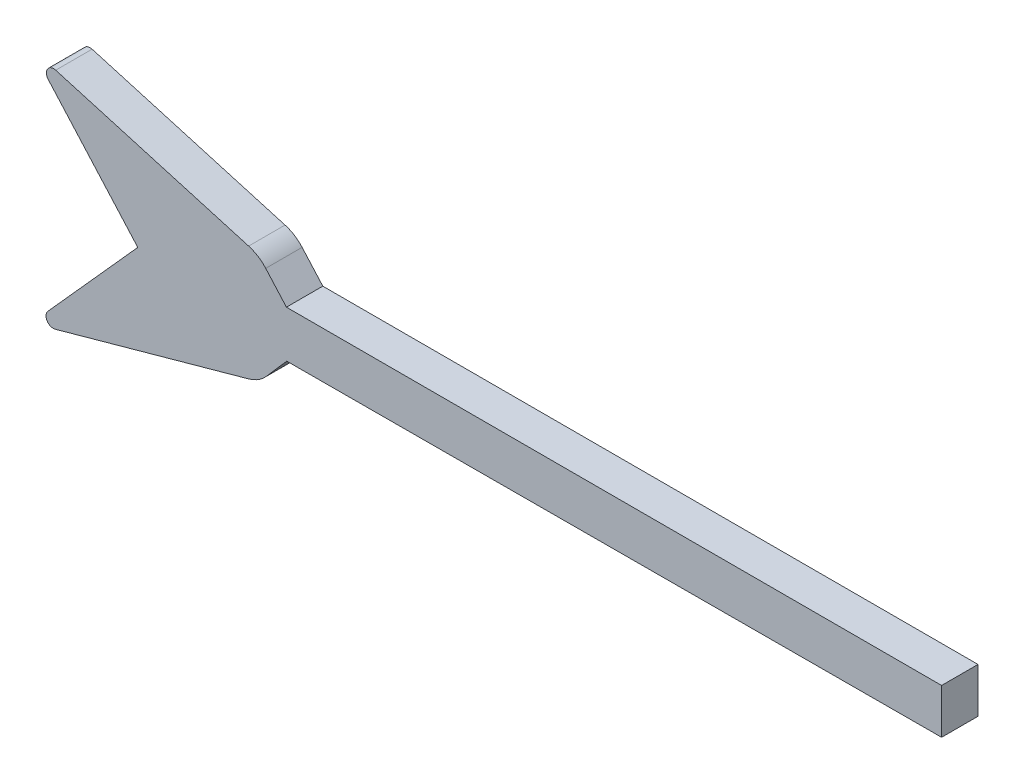
SolidWorks part; units mm, degrees
ref_plane "Plan de face" through (0, 0, 0) normal (0, 0, 1) x (1, 0, 0)
ref_plane "Plan de dessus" through (0, 0, 0) normal (0, 1, 0) x (1, 0, 0)
ref_plane "Plan de droite" through (0, 0, 0) normal (1, 0, 0) x (0, 0, -1)
sketch "Esquisse1" plane through (0, 0, 0) normal (0, 0, 1) x (1, 0, 0)
  line L0 (-12.4551, 7.3291) -> (-23.8324, 20.1144)
  line L1 (-28.5223, 23.0723) -> (-81.5296, 38.4159)
  line L2 (-83.5798, 35.1652) -> (-58.9831, 7.5246)
  line L3 (-58.9831, 7.5246) -> (-83.6838, -20.0231)
  line L4 (-81.6598, -23.2854) -> (-28.5015, -8.5304)
  line L5 (-23.6466, -5.4756) -> (-12.4551, 7.3291)
  line L6 (-18.1437, 13.7217) -> (161.8563, 13.7217)
  line L7 (161.8563, 13.7217) -> (161.8563, 1.3786)
  line L8 (161.8563, 1.3786) -> (-18.0508, 0.9268)
  line L9 (-18.0508, 0.9268) -> (-12.4551, 7.3291)
  arc A0 (-83.6838, -20.0231) -> (-81.6598, -23.2854) centre (-82.1948, -21.3582) ccw
  arc A1 (-81.5296, 38.4159) -> (-83.5798, 35.1652) centre (-82.0857, 36.4947) ccw
  arc A2 (-28.5015, -8.5304) -> (-23.6466, -5.4756) centre (-31.176, 1.1053) ccw
  arc A3 (-23.8324, 20.1144) -> (-28.5223, 23.0723) centre (-31.3028, 13.4666) ccw
  point P8 (-88.2489, -25.1143)
  point P11 (-88.1875, 40.343)
  point P14 (-25.6168, -7.7297)
  point P17 (-25.7506, 22.27)
  dimension "D6" = 2
  dimension "D7" = 10
  dimension "D1" = 30
  dimension "D2" = 20
  dimension "D3" = 20
  dimension "D4" = 65
  dimension "D5" = 65
  dimension "D8" = 12.3431
  dimension "D9" = 180
  dimension "D10" = 37
  dimension "D11" = 37
extrude "Boss.-Extru.1" add sketch "Esquisse1" along normal blind 10 contours L8 L7 L6 L0 L5 | L0 A3 L1 A1 L2 L3 A0 L4 A2 L5 region at (72.7602, 7.4389, 0)
